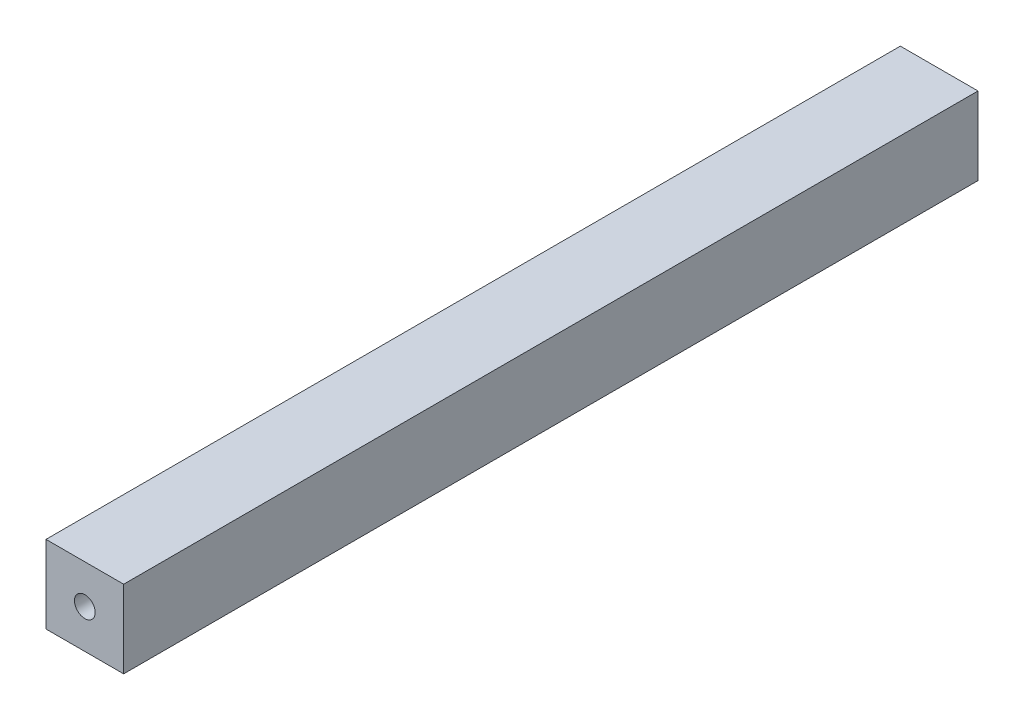
SolidWorks part; units mm, degrees
ref_plane "Front Plane" through (0, 0, 0) normal (0, 0, 1) x (1, 0, 0)
ref_plane "Top Plane" through (0, 0, 0) normal (0, 1, 0) x (1, 0, 0)
ref_plane "Right Plane" through (0, 0, 0) normal (1, 0, 0) x (0, 0, -1)
sketch "Sketch1" plane through (0, 0, 0) normal (0, 0, 1) x (1, 0, 0)
  line L1 (-15, -15) -> (15, -15)
  line L2 (-15, -15) -> (-15, 15)
  line L3 (-15, 15) -> (15, 15)
  line L4 (15, -15) -> (15, 15)
  line L5 (-15, -15) -> (15, 15) construction
  line L6 (-15, 15) -> (15, -15) construction
  point P0 (0, 0)
  dimension "D1" = 30
  dimension "D2" = 30
extrude "Boss-Extrude1" add sketch "Sketch1" along normal mid plane 330
sketch "Sketch2" plane through (0, 0, 165) normal (0, 0, 1) x (1, 0, 0)
  circle A0 centre (0, 0) radius 4
  dimension "D1" = 8
extrude "Cut-Extrude1" cut sketch "Sketch2" against normal through all
